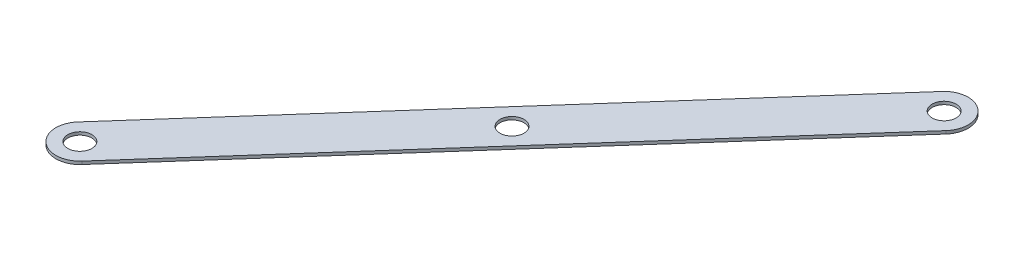
SolidWorks part; units mm, degrees
ref_plane "Front" through (0, 0, 0) normal (0, 0, 1) x (1, 0, 0)
ref_plane "Top" through (0, 0, 0) normal (0, 1, 0) x (1, 0, 0)
ref_plane "Right" through (0, 0, 0) normal (1, 0, 0) x (0, 0, -1)
sketch "Sketch1" plane through (0, 0, 0) normal (0, 1, 0) x (1, 0, 0)
  line L0 (0, 0) -> (214.595, 242.5445) construction
  line L1 (-9.5115, 8.4155) -> (205.0834, 250.96)
  line L2 (9.5115, -8.4155) -> (224.1065, 234.129)
  arc A0 (-9.5115, 8.4155) -> (9.5115, -8.4155) centre (0, 0) ccw
  arc A1 (224.1065, 234.129) -> (205.0834, 250.96) centre (214.595, 242.5445) ccw
  circle A2 centre (107.2975, 121.2722) radius 6.35
  circle A3 centre (214.595, 242.5445) radius 6.35
  circle A4 centre (0, 0) radius 6.35
  point P3 (107.2975, 121.2722)
  dimension "D3" = 12.7
  dimension "D4" = 12.7
  dimension "D5" = 12.7
  dimension "D1" = 323.85
  dimension "D2" = 25.4
extrude "Boss-Extrude1" add sketch "Sketch1" along normal blind 1.5875
